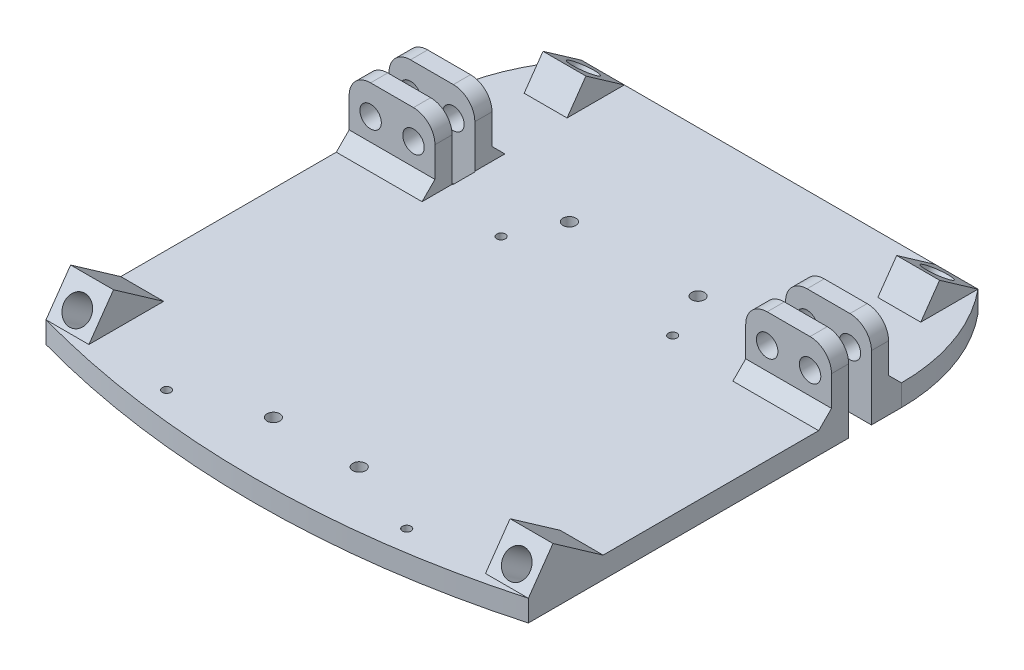
SolidWorks part; units mm, degrees
material "PET"
ref_plane "Front Plane" through (0, 0, 0) normal (0, 0, 1) x (1, 0, 0)
ref_plane "Top Plane" through (0, 0, 0) normal (0, 1, 0) x (1, 0, 0)
ref_plane "Right Plane" through (0, 0, 0) normal (1, 0, 0) x (0, 0, -1)
sketch "Sketch1" plane through (-32.812, 33.9517, -54.9073) normal (0, -1, 0) x (-1, 0, 0)
  line L1 (-55, 35) -> (57.4546, 35)
  line L2 (-55, 35) -> (-55, -85)
  line L3 (-55, -85) -> (57.4546, -85)
  line L4 (57.4546, 35) -> (57.4546, -85)
  line L19 (-34.85, -5.15) -> (-34.85, 0.15)
  line L20 (-34.85, 0.15) -> (-55.15, 0.15)
  line L21 (-55.15, 0.15) -> (-55.15, -5.15)
  line L22 (-55.15, -5.15) -> (-34.85, -5.15)
  line L31 (57.6046, -4.6732) -> (57.6046, 0.6268)
  line L32 (57.6046, 0.6268) -> (37.3046, 0.6268)
  line L33 (37.3046, 0.6268) -> (37.3046, -4.6732)
  line L34 (37.3046, -4.6732) -> (57.6046, -4.6732)
  dimension "D2" = 120
extrude "Boss-Extrude1" add sketch "Sketch1" along normal mid plane 5 contours L34 L33 L32 L4 L1 L2 L20 L19 L22 L3 region at (-34.0393, 33.9517, -29.5417)
sketch "Sketch2" plane through (-90.2666, 0, 0) normal (-1, 0, 0) x (0, 0, 1)
  line L0 (7.4822, 36.4517) -> (19.1809, 44.6433)
  line L2 (-50.2342, 36.4517) -> (30.0927, 36.4517) construction
  line L3 (19.1809, 44.6433) -> (24.9167, 36.4517)
  line L4 (19.833, 41.4375) -> (-62.0822, -15.9201) construction
  line L6 (23.2745, 36.5226) -> (19.833, 41.4375) construction
  line L7 (19.833, 41.4375) -> (-62.0822, -15.9201) construction
  line L8 (7.4822, 36.4517) -> (24.9167, 36.4517)
  dimension "D1" = 3
  dimension "D2" = 10
extrude "Boss-Extrude2" add sketch "Sketch2" against normal blind 10
sketch "Sketch3" plane through (0, 23.6993, 33.8461) normal (0, 0.5736, 0.8192) x (1, 0, 0)
  circle A2 centre (-85.2666, 19.5679) radius 3.1
  circle A3 centre (-85.2666, 19.5679) radius 3.1
  dimension "D1" = 0
extrude "Cut-Extrude1" cut sketch "Sketch3" against normal through all
ref_plane "Plane1" through (-70.2666, 0, 0) normal (1, 0, 0) x (0, 0, -1)
sketch "Sketch4" plane through (-70.2666, 0, 0) normal (1, 0, 0) x (0, 0, -1)
  line L0 (76.5597, 36.4517) -> (80.9509, 42.7231)
  line L1 (89.9073, 36.4517) -> (55.0573, 36.4517) construction
  line L3 (157.7666, 147.1969) -> (43.0513, -16.6335) construction
  line L4 (157.7666, 147.1969) -> (43.0513, -16.6335) construction
  line L5 (76.5597, 36.4517) -> (89.9073, 36.4517)
  line L6 (160.3208, 146.6292) -> (45.6055, -17.2012) construction
  line L7 (80.9509, 42.7231) -> (89.9073, 36.4517)
  dimension "D1" = 3
extrude "Boss-Extrude3" add sketch "Sketch4" against normal blind 10
sketch "Sketch5" plane through (0, 66.7021, -46.7053) normal (0, 0.8192, -0.5736) x (1, 0, 0)
  circle A1 centre (-75.2666, 47.224) radius 3.1
  dimension "D1" = 6.2
extrude "Cut-Extrude2" cut sketch "Sketch5" against normal through all
ref_plane "Plane2" through (-34.0393, 0, 0) normal (-1, 0, 0) x (0, 0, 1)
mirror "Mirror1" about plane through (-34.0393, 0, 0) normal (-1, 0, 0) of "Cut-Extrude2", "Boss-Extrude3", "Cut-Extrude1", "Boss-Extrude2"
sketch "Sketch6" plane through (-90.2666, 0, 0) normal (-1, 0, 0) x (0, 0, 1)
  line L7 (24.9167, 36.4517) -> (24.9167, 31.4517)
  line L8 (24.9167, 31.4517) -> (-55.3238, 31.4517)
  line L14 (7.4822, 36.4517) -> (-50.2342, 36.4517)
  line L15 (-50.2342, 36.4517) -> (-50.2342, 31.4517)
  line L17 (-50.2342, 36.4517) -> (-50.2342, 31.4517)
  line L19 (24.9167, 36.4517) -> (19.1809, 44.6433)
  line L20 (19.1809, 44.6433) -> (7.4822, 36.4517)
  line L21 (7.4822, 36.4517) -> (-50.2342, 36.4517)
  line L26 (24.9167, 36.4517) -> (19.1809, 44.6433)
  line L27 (19.1809, 44.6433) -> (7.4822, 36.4517)
  line L30 (-50.2342, 31.4517) -> (30.0927, 31.4517)
  line L32 (-50.2342, 31.4517) -> (30.0927, 31.4517)
  line L34 (30.0927, 31.4517) -> (30.0927, 36.4517)
  line L35 (30.0927, 31.4517) -> (30.0927, 36.4517)
  line L36 (30.0927, 36.4517) -> (24.9167, 36.4517)
  line L37 (30.0927, 36.4517) -> (24.9167, 36.4517)
  line M10 (-50.2342, 31.4517) -> (30.0927, 31.4517)
  line M11 (30.0927, 31.4517) -> (30.0927, 36.4517)
  line M12 (30.0927, 36.4517) -> (24.9167, 36.4517)
  dimension "D1" = 0
extrude "Cut-Extrude3" cut sketch "Sketch6" against normal through all contours L7 M12 M10 M11 region at (-90.2666, 33.9517, 27.5047)
sketch "Sketch7" plane through (0, 36.4517, 0) normal (0, 1, 0) x (1, 0, 0)
  line L6 (-34.0393, 89.9073) -> (-34.0393, -24.9167) construction
  line L7 (2.188, 89.9073) -> (-70.2666, 89.9073) construction
  line L8 (12.188, -24.9167) -> (-80.2666, -24.9167) construction
  line L9 (22.188, 49.7573) -> (2.038, 49.7573)
  line L10 (2.038, 49.7573) -> (2.038, 55.0573)
  line L11 (2.038, 55.0573) -> (22.188, 55.0573)
  line L12 (22.188, 49.7573) -> (2.038, 49.7573)
  line L13 (2.038, 49.7573) -> (2.038, 55.0573)
  line L14 (2.038, 55.0573) -> (22.188, 55.0573)
  line L15 (-90.2666, 49.7573) -> (-70.1166, 49.7573)
  line L16 (-70.1166, 49.7573) -> (-70.1166, 55.0573)
  line L17 (-70.1166, 55.0573) -> (-90.2666, 55.0573)
  line L42 (-90.2666, 55.5342) -> (-90.2666, 55.0573)
  line L66 (-80.2666, -7.4822) -> (-80.2666, -24.9167)
  line L67 (-80.2666, -24.9167) -> (12.188, -24.9167)
  line L68 (12.188, -24.9167) -> (12.188, -7.4822)
  line L69 (12.188, -7.4822) -> (22.188, -7.4822)
  line L70 (22.188, -7.4822) -> (22.188, 49.7573)
  line L71 (22.188, 49.7573) -> (2.038, 49.7573)
  line L72 (2.038, 49.7573) -> (2.038, 55.0573)
  line L73 (2.038, 55.0573) -> (22.188, 55.0573)
  line L74 (22.188, 55.0573) -> (22.188, 89.9073)
  line L75 (22.188, 89.9073) -> (12.188, 89.9073)
  line L76 (12.188, 89.9073) -> (12.188, 76.5597)
  line L77 (12.188, 76.5597) -> (2.188, 76.5597)
  line L78 (2.188, 76.5597) -> (2.188, 89.9073)
  line L79 (2.188, 89.9073) -> (-70.2666, 89.9073)
  line L80 (-70.2666, 89.9073) -> (-70.2666, 76.5597)
  line L81 (-70.2666, 76.5597) -> (-80.2666, 76.5597)
  line L82 (-80.2666, 76.5597) -> (-80.2666, 89.9073)
  line L83 (-80.2666, 89.9073) -> (-90.2666, 89.9073)
  line L84 (-90.2666, 89.9073) -> (-90.2666, 55.5342)
  line L85 (-90.2666, 55.5342) -> (-70.1166, 55.5342)
  line L86 (-70.1166, 55.5342) -> (-70.1166, 50.2342)
  line L87 (-70.1166, 50.2342) -> (-90.2666, 50.2342)
  line L88 (-90.2666, 50.2342) -> (-90.2666, -7.4822)
  line L89 (-90.2666, -7.4822) -> (-80.2666, -7.4822)
  line L90 (-80.2666, -7.4822) -> (-80.2666, -24.9167)
  line L91 (-80.2666, -24.9167) -> (12.188, -24.9167)
  line L92 (12.188, -24.9167) -> (12.188, -7.4822)
  line L93 (12.188, -7.4822) -> (22.188, -7.4822)
  line L94 (22.188, -7.4822) -> (22.188, 49.7573)
  line L95 (22.188, 49.7573) -> (2.038, 49.7573)
  line L96 (2.038, 49.7573) -> (2.038, 55.0573)
  line L97 (2.038, 55.0573) -> (22.188, 55.0573)
  line L98 (22.188, 55.0573) -> (22.188, 89.9073)
  line L99 (22.188, 89.9073) -> (12.188, 89.9073)
  line L100 (12.188, 89.9073) -> (12.188, 76.5597)
  line L101 (12.188, 76.5597) -> (2.188, 76.5597)
  line L102 (2.188, 76.5597) -> (2.188, 89.9073)
  line L103 (2.188, 89.9073) -> (-70.2666, 89.9073)
  line L104 (-70.2666, 89.9073) -> (-70.2666, 76.5597)
  line L105 (-70.2666, 76.5597) -> (-80.2666, 76.5597)
  line L106 (-80.2666, 76.5597) -> (-80.2666, 89.9073)
  line L107 (-80.2666, 89.9073) -> (-90.2666, 89.9073)
  line L108 (-90.2666, 89.9073) -> (-90.2666, 55.5342)
  line L109 (-90.2666, 55.5342) -> (-70.1166, 55.5342)
  line L110 (-70.1166, 55.5342) -> (-70.1166, 50.2342)
  line L111 (-70.1166, 50.2342) -> (-90.2666, 50.2342)
  line L112 (-90.2666, 50.2342) -> (-90.2666, -7.4822)
  line L113 (-90.2666, -7.4822) -> (-80.2666, -7.4822)
  line M52 (-90.2666, 55.5342) -> (-70.1166, 55.5342)
  line M53 (-70.1166, 55.5342) -> (-70.1166, 50.2342)
  line M54 (-70.1166, 50.2342) -> (-90.2666, 50.2342)
  line M55 (-90.2666, 50.2342) -> (-90.2666, -7.4822)
  dimension "D1" = 0
  dimension "D2" = 0
extrude "Boss-Extrude4" add sketch "Sketch7" against normal up to surface (5 mm away) contours L42 L17 M52 M53 region at (-80.1916, 36.4517, -55.2958) up to face at (-34.0393, 31.4517, -45.9289)
extrude "Cut-Extrude4" cut sketch "Sketch7<3>" against normal up to surface (5 mm away) contours L15 L16 M54 M55 region at (-80.1916, 36.4517, -49.9958) up to face at (-34.0393, 31.4517, -45.8495)
sketch "Sketch7<3>" plane through (0, 36.4517, 0) normal (0, 1, 0) x (1, 0, 0) same geometry as "Sketch7"
sketch "Sketch8" plane through (-90.2666, 0, 0) normal (-1, 0, 0) x (0, 0, 1)
  line L0 (-89.9073, 36.4517) -> (-55.0573, 36.4517) construction
  line L1 (-59.0573, 36.4517) -> (-55.0573, 36.4517)
  line L2 (-59.0573, 36.4517) -> (-59.0573, 51.4517)
  line L3 (-59.0573, 51.4517) -> (-55.0573, 51.4517)
  line L4 (-55.0573, 36.4517) -> (-55.0573, 51.4517)
  line L5 (-55.0573, 31.4517) -> (-55.0573, 36.4517) construction
  line L6 (-52.4073, 31.4517) -> (-52.4073, 36.4517) construction
  line L7 (-55.0573, 31.4517) -> (-49.7573, 31.4517) construction
  line L8 (-55.0573, 36.4517) -> (-49.7573, 36.4517) construction
  line L9 (-45.7573, 51.4517) -> (-49.7573, 51.4517)
  line L10 (-49.7573, 36.4517) -> (-49.7573, 51.4517)
  line L11 (-45.7573, 36.4517) -> (-49.7573, 36.4517)
  line L12 (-45.7573, 36.4517) -> (-45.7573, 51.4517)
  dimension "D1" = 15
  dimension "D2" = 4
extrude "Boss-Extrude5" add sketch "Sketch8" against normal blind 20
sketch "Sketch9" plane through (0, 0, -59.0573) normal (0, 0, -1) x (-1, 0, 0)
  line L0 (75.2666, 44.6433) -> (85.2666, 44.6433) construction
  line L1 (80.2666, 44.6433) -> (80.2666, 51.4517) construction
  line L2 (70.2666, 51.4517) -> (90.2666, 51.4517) construction
  line L3 (85.2666, 44.6433) -> (90.2666, 44.6433) construction
  circle A0 centre (75.2666, 44.6433) radius 2.5
  circle A1 centre (85.2666, 44.6433) radius 2.5
  dimension "D1" = 5
  dimension "D2" = 5
  dimension "D3" = 10
extrude "Cut-Extrude5" cut sketch "Sketch9" against normal up to surface (13.3 mm away) up to face at (-80.2666, 43.9517, -45.7573)
fillet "Fillet1" radius 5 4 edges at (-90.2666, 51.4517, -57.0573) (-90.2666, 51.4517, -47.7573) (-70.2666, 51.4517, -57.0573) (-70.2666, 51.4517, -47.7573)
chamfer "Chamfer1" distance 3 angle 45 2 edges at (-80.2666, 36.4517, -59.0573) (-80.2666, 36.4517, -45.7573)
mirror "Mirror2" about plane through (-34.0393, 0, 0) normal (-1, 0, 0) of "Chamfer1", "Fillet1", "Boss-Extrude4", "Cut-Extrude4", "Boss-Extrude5", "Cut-Extrude5"
sketch "Sketch10" plane through (0, 36.4517, 0) normal (0, 1, 0) x (1, 0, 0)
  line L0 (-34.0393, -24.9167) -> (-34.0393, -52.8499) construction
  line L1 (12.188, -24.9167) -> (-80.2666, -24.9167) construction
  line L2 (-90.2666, -24.9167) -> (22.188, -24.9167)
  arc A0 (-90.2666, -24.9167) -> (22.188, -24.9167) centre (-34.0393, 177.4159) ccw
  dimension "D1" = 210
extrude "Boss-Extrude6" add sketch "Sketch10" against normal up to surface (5 mm away) up to face at (-34.0393, 31.4517, -45.77)
sketch "Sketch11" plane through (0, 36.4517, 0) normal (0, 1, 0) x (1, 0, 0)
  circle A0 centre (-54.0393, 44.9512) radius 1
  circle A1 centre (-14.0393, 44.9512) radius 1
  circle A2 centre (-6.0393, -25.0488) radius 1
  circle A3 centre (-62.0393, -25.0488) radius 1
  dimension "D1" = 2
  dimension "D2" = 2
  dimension "D3" = 2
  dimension "D4" = 2
extrude "Cut-Extrude6" cut sketch "Sketch11" against normal through all
sketch "Sketch12" plane through (0, 31.4517, 0) normal (0, -1, 0) x (1, 0, 0)
  line L0 (-34.0393, 32.5841) -> (-34.0393, -89.9073) construction
  line L1 (22.188, -89.9073) -> (-90.2666, -89.9073) construction
  line L2 (-11.0952, -55.8736) -> (-57.0952, -55.8736) construction
  line L3 (-55.5572, 18.1264) -> (-15.5572, 18.1264) construction
  arc A0 (22.188, 24.9167) -> (-90.2666, 24.9167) centre (-34.0393, -177.4159) ccw construction
  circle A1 centre (-19.0393, -55.8736) radius 1.5
  circle A2 centre (-24.0393, 18.1264) radius 1.5
  circle A3 centre (-49.0393, -55.8736) radius 1.5
  circle A4 centre (-44.0393, 18.1264) radius 1.5
  dimension "D1" = 3
  dimension "D3" = 10
  dimension "D4" = 3
  dimension "D2" = 15
extrude "Cut-Extrude7" cut sketch "Sketch12" against normal through all
sketch "Sketch13" plane through (0, 36.4517, 0) normal (0, 1, 0) x (1, 0, 0)
  line L66 (2.188, 55.0573) -> (2.188, 62.0573)
  line L67 (2.188, 62.0573) -> (22.188, 62.0573)
  line L68 (22.188, 62.0573) -> (22.188, 89.9073)
  line L69 (22.188, 89.9073) -> (12.188, 89.9073)
  line L70 (12.188, 89.9073) -> (12.188, 76.5597)
  line L71 (12.188, 76.5597) -> (2.188, 76.5597)
  line L72 (2.188, 76.5597) -> (2.188, 89.9073)
  line L73 (2.188, 89.9073) -> (-70.2666, 89.9073)
  line L74 (-70.2666, 89.9073) -> (-70.2666, 76.5597)
  line L75 (-70.2666, 76.5597) -> (-80.2666, 76.5597)
  line L76 (-80.2666, 76.5597) -> (-80.2666, 89.9073)
  line L77 (-80.2666, 89.9073) -> (-90.2666, 89.9073)
  line L78 (-90.2666, 89.9073) -> (-90.2666, 62.0573)
  line L79 (-90.2666, 62.0573) -> (-70.2666, 62.0573)
  line L80 (-70.2666, 62.0573) -> (-70.2666, 55.0573)
  line L81 (-70.2666, 55.0573) -> (-70.1166, 55.0573)
  line L82 (-70.1166, 55.0573) -> (-70.1166, 49.7573)
  line L83 (-70.1166, 49.7573) -> (-70.2666, 49.7573)
  line L84 (-70.2666, 49.7573) -> (-70.2666, 42.7573)
  line L85 (-70.2666, 42.7573) -> (-90.2666, 42.7573)
  line L86 (-90.2666, 42.7573) -> (-90.2666, -7.4822)
  line L87 (-90.2666, -7.4822) -> (-80.2666, -7.4822)
  line L88 (-80.2666, -7.4822) -> (-80.2666, -24.9167)
  line L89 (-80.2666, -24.9167) -> (-90.2666, -24.9167)
  line L90 (22.188, -24.9167) -> (12.188, -24.9167)
  line L91 (12.188, -24.9167) -> (12.188, -7.4822)
  line L92 (12.188, -7.4822) -> (22.188, -7.4822)
  line L93 (22.188, -7.4822) -> (22.188, 42.7573)
  line L94 (22.188, 42.7573) -> (2.188, 42.7573)
  line L95 (2.188, 42.7573) -> (2.188, 49.7573)
  line L96 (2.188, 49.7573) -> (2.038, 49.7573)
  line L97 (2.038, 49.7573) -> (2.038, 55.0573)
  line L98 (2.038, 55.0573) -> (2.188, 55.0573)
  line L99 (2.188, 55.0573) -> (2.188, 62.0573)
  line L100 (2.188, 62.0573) -> (22.188, 62.0573)
  line L101 (22.188, 62.0573) -> (22.188, 89.9073)
  line L102 (22.188, 89.9073) -> (12.188, 89.9073)
  line L103 (12.188, 89.9073) -> (12.188, 76.5597)
  line L104 (12.188, 76.5597) -> (2.188, 76.5597)
  line L105 (2.188, 76.5597) -> (2.188, 89.9073)
  line L106 (2.188, 89.9073) -> (-70.2666, 89.9073)
  line L107 (-70.2666, 89.9073) -> (-70.2666, 76.5597)
  line L108 (-70.2666, 76.5597) -> (-80.2666, 76.5597)
  line L109 (-80.2666, 76.5597) -> (-80.2666, 89.9073)
  line L110 (-80.2666, 89.9073) -> (-90.2666, 89.9073)
  line L111 (-90.2666, 89.9073) -> (-90.2666, 62.0573)
  line L112 (-90.2666, 62.0573) -> (-70.2666, 62.0573)
  line L113 (-70.2666, 62.0573) -> (-70.2666, 55.0573)
  line L114 (-70.2666, 55.0573) -> (-70.1166, 55.0573)
  line L115 (-70.1166, 55.0573) -> (-70.1166, 49.7573)
  line L116 (-70.1166, 49.7573) -> (-70.2666, 49.7573)
  line L117 (-70.2666, 49.7573) -> (-70.2666, 42.7573)
  line L118 (-70.2666, 42.7573) -> (-90.2666, 42.7573)
  line L119 (-90.2666, 42.7573) -> (-90.2666, -7.4822)
  line L120 (-90.2666, -7.4822) -> (-80.2666, -7.4822)
  line L121 (-80.2666, -7.4822) -> (-80.2666, -24.9167)
  line L122 (-80.2666, -24.9167) -> (-90.2666, -24.9167)
  line L123 (22.188, -24.9167) -> (12.188, -24.9167)
  line L124 (12.188, -24.9167) -> (12.188, -7.4822)
  line L125 (12.188, -7.4822) -> (22.188, -7.4822)
  line L126 (22.188, -7.4822) -> (22.188, 42.7573)
  line L127 (22.188, 42.7573) -> (2.188, 42.7573)
  line L128 (2.188, 42.7573) -> (2.188, 49.7573)
  line L129 (2.188, 49.7573) -> (2.038, 49.7573)
  line L130 (2.038, 49.7573) -> (2.038, 55.0573)
  line L131 (2.038, 55.0573) -> (2.188, 55.0573)
  arc A1 (-90.2666, 62.0573) -> (-80.2666, 89.9073) centre (-46.4855, 62.0573) cw
  arc A2 (-90.2666, -24.9167) -> (22.188, -24.9167) centre (-34.0393, 177.4159) ccw
  arc A3 (-90.2666, -24.9167) -> (22.188, -24.9167) centre (-34.0393, 177.4159) ccw
  arc A4 (22.188, 62.0573) -> (12.188, 89.9073) centre (-21.5932, 62.0573) ccw
  line M45 (22.188, 62.0573) -> (22.188, 89.9073)
  line M46 (22.188, 89.9073) -> (12.188, 89.9073)
  line M54 (-80.2666, 89.9073) -> (-90.2666, 89.9073)
  line M55 (-90.2666, 89.9073) -> (-90.2666, 62.0573)
  dimension "D1" = 0
extrude "Cut-Extrude8" cut sketch "Sketch13" against normal through all contours A1 M55 M54 | A4 M45 M46 region at (19.2575, 36.4517, -83.1139) region at (-87.3361, 36.4517, -83.1139)
